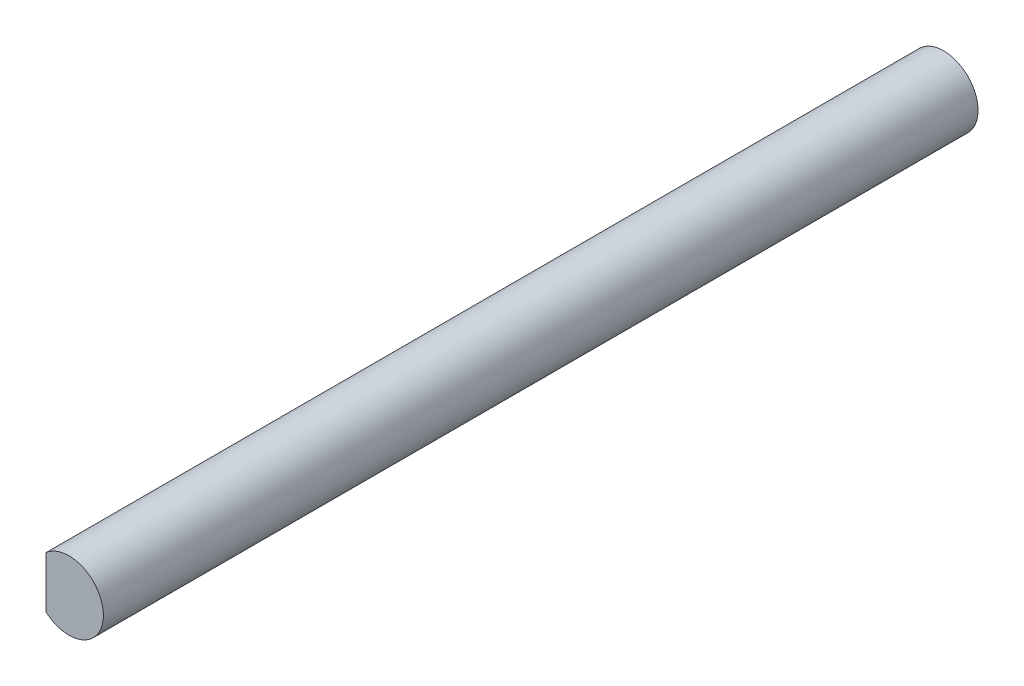
SolidWorks part; units mm, degrees
ref_plane "Front Plane" through (0, 0, 0) normal (0, 0, 1) x (1, 0, 0)
ref_plane "Top Plane" through (0, 0, 0) normal (0, 1, 0) x (1, 0, 0)
ref_plane "Right Plane" through (0, 0, 0) normal (1, 0, 0) x (0, 0, -1)
sketch "Sketch1" plane through (0, 0, 0) normal (0, 0, 1) x (1, 0, 0)
  line L1 (-2, 2.2361) -> (-2, -2.2361)
  arc A0 (-2, -2.2361) -> (-2, 2.2361) centre (0, 0) ccw
  dimension "D1" = 6
extrude "Boss-Extrude1" add sketch "Sketch1" along normal blind 76.2
